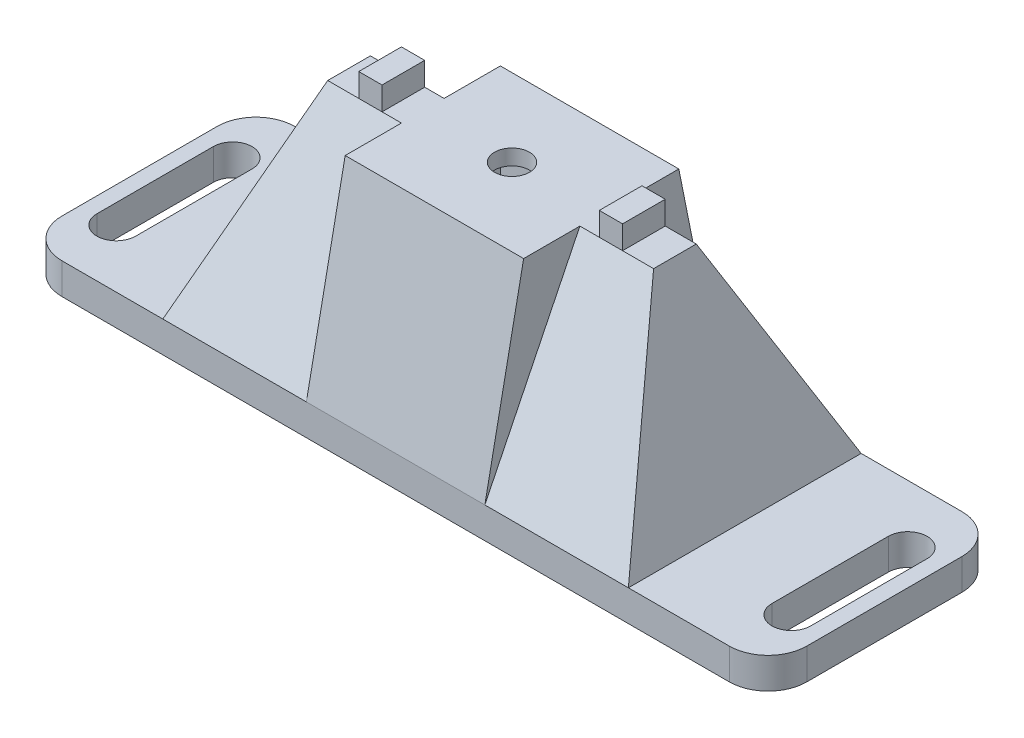
SolidWorks part; units mm, degrees
ref_plane "Front Plane" through (0, 0, 0) normal (0, 0, 1) x (1, 0, 0)
ref_plane "Top Plane" through (0, 0, 0) normal (0, 1, 0) x (1, 0, 0)
ref_plane "Right Plane" through (0, 0, 0) normal (1, 0, 0) x (0, 0, -1)
sketch "Sketch2" plane through (0, 0, 0) normal (0, 1, 0) x (1, 0, 0)
  line L0 (-43.5, -7.5) -> (-43.5, 7.5) construction
  line L1 (-43, 15) -> (43, 15)
  line L2 (-48, 10) -> (-48, -10)
  line L3 (-43, -15) -> (43, -15)
  line L4 (48, 10) -> (48, -10)
  line L5 (0, -15) -> (0, 15) construction
  line L6 (-48, 0) -> (48, 0) construction
  line L7 (-46, -7.5) -> (-46, 7.5)
  line L8 (-41, -7.5) -> (-41, 7.5)
  line L9 (43.5, -7.5) -> (43.5, 7.5) construction
  line L10 (46, -7.5) -> (46, 7.5)
  line L11 (41, -7.5) -> (41, 7.5)
  arc A0 (-46, -7.5) -> (-41, -7.5) centre (-43.5, -7.5) ccw
  arc A1 (-41, 7.5) -> (-46, 7.5) centre (-43.5, 7.5) ccw
  arc A2 (46, -7.5) -> (41, -7.5) centre (43.5, -7.5) cw
  arc A3 (41, 7.5) -> (46, 7.5) centre (43.5, 7.5) cw
  arc A4 (-43, 15) -> (-48, 10) centre (-43, 10) ccw
  arc A5 (-48, -10) -> (-43, -15) centre (-43, -10) ccw
  arc A6 (43, 15) -> (48, 10) centre (43, 10) cw
  arc A7 (43, -15) -> (48, -10) centre (43, -10) ccw
  point P0 (0, 0)
  point P6 (-43.5, 0)
  point P14 (0, 0)
  point P15 (-77.6113, 0)
  point P16 (-77.9757, 0)
  point P17 (-41, 7.2267)
  point P20 (43.5, 0)
  point P27 (-48, 15)
  point P30 (-48, -15)
  point P33 (48, 15)
  dimension "D6" = 5
  dimension "D1" = 30
  dimension "D2" = 96
  dimension "D3" = 5
  dimension "D4" = 2
  dimension "D5" = 15
extrude "Boss-Extrude1" add sketch "Sketch2" against normal blind 4
sketch "Sketch3" plane through (0, 0, 0) normal (1, 0, 0) x (0, 0, -1)
  line L0 (-15, 0) -> (-2.75, 25)
  line L1 (-2.75, 25) -> (2.75, 25)
  line L2 (2.75, 25) -> (15, 0)
  line L3 (-10, 0) -> (10, 0) construction
  line L4 (-15, 0) -> (-10, 25)
  line L5 (-10, 25) -> (10, 25)
  line L6 (10, 25) -> (15, 0)
  line L7 (-15, 0) -> (15, 0)
  point P3 (0, 25)
  point P10 (0, 25)
  dimension "D1" = 5.5
  dimension "D2" = 25
  dimension "D3" = 20
extrude "Boss-Extrude2" add sketch "Sketch3" along normal mid plane 60 contours L0 L7 L2 L1 region at (0, 9.6244, 0)
extrude "Boss-Extrude3" add sketch "Sketch3<3>" along normal mid plane 23 contours L5 L4 L0 | L6 L5 L2 region at (0, 16.6667, 9.25) region at (0, 16.6667, -9.25)
sketch "Sketch3<3>" plane through (0, 0, 0) normal (1, 0, 0) x (0, 0, -1) same geometry as "Sketch3"
sketch "Sketch4" plane through (0, 0, 0) normal (0, 0, 1) x (1, 0, 0)
  line L0 (11.5, 25) -> (11.5, 0) construction
  line L1 (11.5, 0) -> (30, 0) construction
  line L2 (30, 0) -> (30, 25) construction
  line L3 (30, 25) -> (11.5, 25) construction
  line L4 (-11.5, 25) -> (-11.5, 0) construction
  line L5 (-11.5, 0) -> (11.5, 0) construction
  line L6 (11.5, 0) -> (11.5, 25) construction
  line L7 (11.5, 25) -> (-11.5, 25) construction
  line L8 (-30, 0) -> (-11.5, 0) construction
  line L9 (-11.5, 0) -> (-11.5, 25) construction
  line L10 (-11.5, 25) -> (-30, 25) construction
  line L11 (-30, 25) -> (-30, 0) construction
  line L12 (11.5, 25) -> (11.5, 0)
  line L13 (11.5, 0) -> (30, 0)
  line L14 (30, 0) -> (30, 25)
  line L15 (30, 25) -> (11.5, 25)
  line L16 (-11.5, 25) -> (-11.5, 0)
  line L17 (-11.5, 0) -> (11.5, 0)
  line L18 (11.5, 0) -> (11.5, 25)
  line L19 (11.5, 25) -> (-11.5, 25)
  line L20 (-30, 0) -> (-11.5, 0)
  line L21 (-11.5, 0) -> (-11.5, 25)
  line L22 (-11.5, 25) -> (-30, 25)
  line L23 (-30, 25) -> (-30, 0)
  line L24 (-30, 0) -> (-21, 25)
  line L25 (30, 0) -> (21, 25)
  line L26 (-21, 25) -> (21, 25) construction
  line L27 (0, 0) -> (0, 25) construction
  line L28 (-17, 25) -> (-14, 25)
  line L29 (-17, 25) -> (-17, 28)
  line L30 (-17, 28) -> (-14, 28)
  line L31 (-14, 25) -> (-14, 28)
  line L32 (14, 25) -> (14, 28)
  line L33 (17, 28) -> (14, 28)
  line L34 (17, 25) -> (17, 28)
  point P9 (0, 25)
  dimension "D1" = 42
  dimension "D2" = 4
  dimension "D3" = 3
  dimension "D4" = 3
extrude "Cut-Extrude1" cut sketch "Sketch4" against normal through all both and the other way through all contours L25 L14 L15 | L23 L24 L22 region at (27, 16.6667, 0) region at (-27, 16.6667, 0)
extrude "Boss-Extrude4" add sketch "Sketch4<3>" along normal mid plane 5.5 contours L15 L34 L33 L32 | L22 L31 L30 L29 region at (15.5, 26.5, 0) region at (-15.5, 26.5, 0)
sketch "Sketch4<3>" plane through (0, 0, 0) normal (0, 0, 1) x (1, 0, 0) same geometry as "Sketch4"
sketch "Sketch5" plane through (0, -4, 0) normal (0, -1, 0) x (1, 0, 0)
  line L0 (-11.5, 2.75) -> (-11.5, -2.75)
  line L1 (11.5, 2.75) -> (11.5, -2.75)
  line L3 (-10.5, 9) -> (10.5, 9)
  line L4 (-10.5, 9) -> (-10.5, -9)
  line L5 (-10.5, -9) -> (10.5, -9)
  line L6 (10.5, 9) -> (10.5, -9)
  line L7 (0, -9) -> (0, 9) construction
  line L8 (-10.5, 0) -> (10.5, 0) construction
  line L12 (14, 2.75) -> (11.5, 2.75)
  line L13 (14, -2.75) -> (14, 2.75)
  line L14 (11.5, -2.75) -> (14, -2.75)
  line L15 (11.5, -10) -> (11.5, -2.75)
  line L16 (-11.5, -10) -> (11.5, -10)
  line L17 (-11.5, -2.75) -> (-11.5, -10)
  line L18 (-14, -2.75) -> (-11.5, -2.75)
  line L19 (-14, 2.75) -> (-14, -2.75)
  line L20 (-11.5, 2.75) -> (-14, 2.75)
  line L21 (-11.5, 10) -> (-11.5, 2.75)
  line L22 (11.5, 10) -> (-11.5, 10)
  line L23 (11.5, 2.75) -> (11.5, 10)
  line L24 (14, 2.75) -> (11.5, 2.75)
  line L25 (14, -2.75) -> (14, 2.75)
  line L26 (11.5, -2.75) -> (14, -2.75)
  line L27 (11.5, -10) -> (11.5, -2.75)
  line L28 (-11.5, -10) -> (11.5, -10)
  line L29 (-11.5, -2.75) -> (-11.5, -10)
  line L30 (-14, -2.75) -> (-11.5, -2.75)
  line L31 (-14, 2.75) -> (-14, -2.75)
  line L32 (-11.5, 2.75) -> (-14, 2.75)
  line L33 (-11.5, 10) -> (-11.5, 2.75)
  line L34 (11.5, 10) -> (-11.5, 10)
  line L35 (11.5, 2.75) -> (11.5, 10)
  point P2 (0, 0)
  dimension "D2" = 18
  dimension "D3" = 21
  dimension "D1" = 0
extrude "Cut-Extrude3" cut sketch "Sketch5" against normal offset from surface (27 mm away) 2 contours L6 L3 L4 L5 region at (0, -4, 0) up to face at (0, 25, 0)
hole_wizard "M4 Clearance Hole1" positions "Sketch6" profile "Sketch7" hole size "M4" standard "ISO" end condition through all
sketch "Sketch6" plane through (0, 25, 0) normal (0, 1, 0) x (1, 0, 0)
  point P0 (0, 0)
sketch "Sketch7" plane through (0, 25, 0) normal (1, 0, 0) x (0, 0, 1)
  line L0 (0, 0) -> (0, 29)
  line L1 (0, 29) -> (2.25, 29)
  line L2 (2.25, 29) -> (2.25, 0)
  line L5 (2.25, 0) -> (0, 0)
  line L11 (0, -6.35) -> (0, 107.95) construction
  dimension "Thru Hole Dia." = 4.5
  dimension "Thru Hole Depth" = 29
